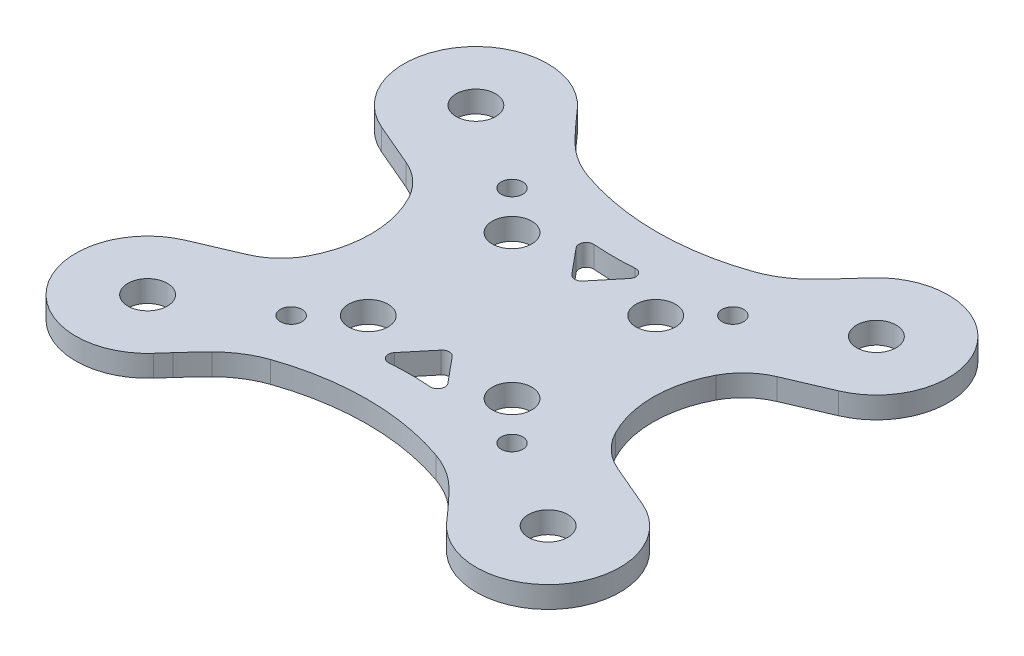
SolidWorks part; units mm, degrees
material "Thornel Mat VMA"
ref_plane "Front Plane" through (0, 0, 0) normal (0, 0, 1) x (1, 0, 0)
ref_plane "Top Plane" through (0, 0, 0) normal (0, 1, 0) x (1, 0, 0)
ref_plane "Right Plane" through (0, 0, 0) normal (1, 0, 0) x (0, 0, -1)
sketch "Sketch1" plane through (0, 0, 0) normal (0, 1, 0) x (1, 0, 0)
  line L0 (19.1123, 28.0515) -> (20.403, 29.4979)
  line L1 (31.7968, 13.6457) -> (25.7944, 11.0784)
  line L2 (25.7944, -11.0784) -> (31.7968, -13.6457)
  line L3 (20.403, -29.4979) -> (19.1123, -28.0515)
  line L4 (-19.1123, -28.0515) -> (-20.403, -29.4979)
  line L5 (-31.7968, -13.6457) -> (-25.7944, -11.0784)
  line L6 (-25.7944, 11.0784) -> (-31.7968, 13.6457)
  line L7 (-20.403, 29.4979) -> (-19.1123, 28.0515)
  line L8 (-0.7696, 9.0904) -> (-3.7105, 12.6352)
  line L9 (3.7105, 12.6352) -> (0.7696, 9.0904)
  line L10 (0.7696, -9.0904) -> (3.7105, -12.6352)
  line L11 (-3.7105, -12.6352) -> (-0.7696, -9.0904)
  circle A0 centre (27.8644, -22.84) radius 2.75
  circle A1 centre (-15.365, -15.365) radius 1.5
  circle A2 centre (15.365, 15.365) radius 1.5
  circle A3 centre (-15.365, 15.365) radius 1.5
  circle A4 centre (27.8644, 22.84) radius 2.75
  circle A5 centre (15.365, -15.365) radius 1.5
  circle A6 centre (10, 10) radius 2.75
  circle A7 centre (-10, 10) radius 2.75
  circle A8 centre (-10, -10) radius 2.75
  circle A9 centre (-27.8644, -22.84) radius 2.75
  circle A10 centre (-27.8644, 22.84) radius 2.75
  circle A11 centre (10, -10) radius 2.75
  arc A12 (16.4739, 25.2397) -> (19.1123, 28.0515) centre (-38.3402, 79.3175) ccw
  arc A13 (25.7944, 11.0784) -> (21.3765, 7.0088) centre (29.3336, 2.8035) ccw
  arc A14 (21.3765, 7.0088) -> (21.3765, -7.0088) centre (34.6384, 0) ccw
  arc A15 (21.3765, -7.0088) -> (25.7944, -11.0784) centre (29.3336, -2.8035) ccw
  arc A16 (20.403, -29.4979) -> (31.7968, -13.6457) centre (27.8644, -22.84) ccw
  arc A17 (19.1123, -28.0515) -> (16.4739, -25.2397) centre (-38.3402, -79.3175) ccw
  arc A18 (16.4739, -25.2397) -> (11.4857, -22.0897) centre (7.2196, -34.3697) ccw
  arc A19 (11.4857, -22.0897) -> (-11.4857, -22.0897) centre (0, -55.1514) ccw
  arc A20 (-11.4857, -22.0897) -> (-16.4739, -25.2397) centre (-7.2196, -34.3697) ccw
  arc A21 (-16.4739, -25.2397) -> (-19.1123, -28.0515) centre (38.3402, -79.3175) ccw
  arc A22 (-31.7968, -13.6457) -> (-20.403, -29.4979) centre (-27.8644, -22.84) ccw
  arc A23 (-25.7944, -11.0784) -> (-21.3765, -7.0088) centre (-29.3336, -2.8035) ccw
  arc A24 (-21.3765, -7.0088) -> (-21.3765, 7.0088) centre (-34.6384, 0) ccw
  arc A25 (-21.3765, 7.0088) -> (-25.7944, 11.0784) centre (-29.3336, 2.8035) ccw
  arc A26 (-20.403, 29.4979) -> (-31.7968, 13.6457) centre (-27.8644, 22.84) ccw
  arc A27 (-19.1123, 28.0515) -> (-16.4739, 25.2397) centre (38.3402, 79.3175) ccw
  arc A28 (-16.4739, 25.2397) -> (-11.4857, 22.0897) centre (-7.2196, 34.3697) ccw
  arc A29 (-11.4857, 22.0897) -> (11.4857, 22.0897) centre (0, 55.1514) ccw
  arc A30 (11.4857, 22.0897) -> (16.4739, 25.2397) centre (7.2196, 34.3697) ccw
  arc A31 (-0.7696, 9.0904) -> (0.7696, 9.0904) centre (0, 9.7289) ccw
  arc A32 (3.7105, 12.6352) -> (2.8655, 14.2709) centre (2.9409, 13.2737) ccw
  arc A33 (-2.8655, 14.2709) -> (2.8655, 14.2709) centre (0, 52.1627) ccw
  arc A34 (-2.8655, 14.2709) -> (-3.7105, 12.6352) centre (-2.9409, 13.2737) ccw
  arc A35 (2.8655, -14.2709) -> (3.7105, -12.6352) centre (2.9409, -13.2737) ccw
  arc A36 (0.7696, -9.0904) -> (-0.7696, -9.0904) centre (0, -9.7289) ccw
  arc A37 (-3.7105, -12.6352) -> (-2.8655, -14.2709) centre (-2.9409, -13.2737) ccw
  arc A38 (2.8655, -14.2709) -> (-2.8655, -14.2709) centre (0, -52.1627) ccw
  arc A39 (31.7968, 13.6457) -> (20.403, 29.4979) centre (27.8644, 22.84) ccw
sketch "Sketch2" plane through (0, 0, 0) normal (0, 1, 0) x (1, 0, 0)
  line L2 (3.7105, -12.6352) -> (0.7696, -9.0904)
  line L3 (-0.7696, -9.0904) -> (-3.7105, -12.6352)
  line L4 (3.7105, -12.6352) -> (0.7696, -9.0904)
  line L5 (-0.7696, -9.0904) -> (-3.7105, -12.6352)
  line L6 (-3.7105, 12.6352) -> (-0.7696, 9.0904)
  line L7 (0.7696, 9.0904) -> (3.7105, 12.6352)
  line L8 (-20.403, -29.4979) -> (-19.1123, -28.0515)
  line L9 (-25.7944, -11.0784) -> (-31.7968, -13.6457)
  line L10 (-31.7968, 13.6457) -> (-25.7944, 11.0784)
  line L11 (-19.1123, 28.0515) -> (-20.403, 29.4979)
  line L12 (20.403, 29.4979) -> (19.1123, 28.0515)
  line L13 (25.7944, 11.0784) -> (31.7968, 13.6457)
  line L14 (31.7968, -13.6457) -> (25.7944, -11.0784)
  line L15 (19.1123, -28.0515) -> (20.403, -29.4979)
  line L16 (-20.403, -29.4979) -> (-19.1123, -28.0515)
  line L17 (-25.7944, -11.0784) -> (-31.7968, -13.6457)
  line L18 (-31.7968, 13.6457) -> (-25.7944, 11.0784)
  line L19 (-19.1123, 28.0515) -> (-20.403, 29.4979)
  line L20 (20.403, 29.4979) -> (19.1123, 28.0515)
  line L21 (25.7944, 11.0784) -> (31.7968, 13.6457)
  line L22 (31.7968, -13.6457) -> (25.7944, -11.0784)
  line L23 (19.1123, -28.0515) -> (20.403, -29.4979)
  line L24 (-3.7105, 12.6352) -> (-0.7696, 9.0904)
  line L25 (0.7696, 9.0904) -> (3.7105, 12.6352)
  circle A1 centre (15.365, -15.365) radius 1.5
  circle A2 centre (15.365, -15.365) radius 1.5
  circle A3 centre (27.8644, 22.84) radius 2.75
  circle A4 centre (27.8644, 22.84) radius 2.75
  circle A5 centre (-15.365, 15.365) radius 1.5
  circle A6 centre (-15.365, 15.365) radius 1.5
  circle A7 centre (15.365, 15.365) radius 1.5
  circle A8 centre (15.365, 15.365) radius 1.5
  circle A9 centre (-15.365, -15.365) radius 1.5
  circle A10 centre (-15.365, -15.365) radius 1.5
  circle A11 centre (27.8644, -22.84) radius 2.75
  circle A12 centre (27.8644, -22.84) radius 2.75
  circle A13 centre (10, -10) radius 2.75
  circle A14 centre (10, -10) radius 2.75
  circle A15 centre (-27.8644, 22.84) radius 2.75
  circle A16 centre (-27.8644, 22.84) radius 2.75
  circle A17 centre (-27.8644, -22.84) radius 2.75
  circle A18 centre (-27.8644, -22.84) radius 2.75
  circle A19 centre (-10, -10) radius 2.75
  circle A20 centre (-10, -10) radius 2.75
  circle A21 centre (-10, 10) radius 2.75
  circle A22 centre (-10, 10) radius 2.75
  circle A23 centre (10, 10) radius 2.75
  circle A24 centre (10, 10) radius 2.75
  arc A28 (2.8655, -14.2709) -> (3.7105, -12.6352) centre (2.9409, -13.2737) ccw
  arc A29 (0.7696, -9.0904) -> (-0.7696, -9.0904) centre (0, -9.7289) ccw
  arc A30 (-3.7105, -12.6352) -> (-2.8655, -14.2709) centre (-2.9409, -13.2737) ccw
  arc A31 (2.8655, -14.2709) -> (-2.8655, -14.2709) centre (0, -52.1627) ccw
  arc A32 (2.8655, -14.2709) -> (3.7105, -12.6352) centre (2.9409, -13.2737) ccw
  arc A33 (0.7696, -9.0904) -> (-0.7696, -9.0904) centre (0, -9.7289) ccw
  arc A34 (-3.7105, -12.6352) -> (-2.8655, -14.2709) centre (-2.9409, -13.2737) ccw
  arc A35 (2.8655, -14.2709) -> (-2.8655, -14.2709) centre (0, -52.1627) ccw
  arc A36 (-2.8655, 14.2709) -> (2.8655, 14.2709) centre (0, 52.1627) ccw
  arc A37 (-2.8655, 14.2709) -> (-3.7105, 12.6352) centre (-2.9409, 13.2737) ccw
  arc A38 (-0.7696, 9.0904) -> (0.7696, 9.0904) centre (0, 9.7289) ccw
  arc A39 (3.7105, 12.6352) -> (2.8655, 14.2709) centre (2.9409, 13.2737) ccw
  arc A40 (-2.8655, 14.2709) -> (2.8655, 14.2709) centre (0, 52.1627) ccw
  arc A41 (-2.8655, 14.2709) -> (-3.7105, 12.6352) centre (-2.9409, 13.2737) ccw
  arc A42 (-0.7696, 9.0904) -> (0.7696, 9.0904) centre (0, 9.7289) ccw
  arc A43 (3.7105, 12.6352) -> (2.8655, 14.2709) centre (2.9409, 13.2737) ccw
  arc A44 (-16.4739, -25.2397) -> (-19.1123, -28.0515) centre (38.3402, -79.3175) ccw
  arc A45 (-31.7968, -13.6457) -> (-20.403, -29.4979) centre (-27.8644, -22.84) ccw
  arc A46 (-25.7944, -11.0784) -> (-21.3765, -7.0088) centre (-29.3336, -2.8035) ccw
  arc A47 (-21.3765, -7.0088) -> (-21.3765, 7.0088) centre (-34.6384, 0) ccw
  arc A48 (-21.3765, 7.0088) -> (-25.7944, 11.0784) centre (-29.3336, 2.8035) ccw
  arc A49 (-20.403, 29.4979) -> (-31.7968, 13.6457) centre (-27.8644, 22.84) ccw
  arc A50 (-19.1123, 28.0515) -> (-16.4739, 25.2397) centre (38.3402, 79.3175) ccw
  arc A51 (-16.4739, 25.2397) -> (-11.4857, 22.0897) centre (-7.2196, 34.3697) ccw
  arc A52 (-11.4857, 22.0897) -> (11.4857, 22.0897) centre (0, 55.1514) ccw
  arc A53 (11.4857, 22.0897) -> (16.4739, 25.2397) centre (7.2196, 34.3697) ccw
  arc A54 (16.4739, 25.2397) -> (19.1123, 28.0515) centre (-38.3402, 79.3175) ccw
  arc A55 (31.7968, 13.6457) -> (20.403, 29.4979) centre (27.8644, 22.84) ccw
  arc A56 (25.7944, 11.0784) -> (21.3765, 7.0088) centre (29.3336, 2.8035) ccw
  arc A57 (21.3765, 7.0088) -> (21.3765, -7.0088) centre (34.6384, 0) ccw
  arc A58 (21.3765, -7.0088) -> (25.7944, -11.0784) centre (29.3336, -2.8035) ccw
  arc A59 (20.403, -29.4979) -> (31.7968, -13.6457) centre (27.8644, -22.84) ccw
  arc A60 (19.1123, -28.0515) -> (16.4739, -25.2397) centre (-38.3402, -79.3175) ccw
  arc A61 (16.4739, -25.2397) -> (11.4857, -22.0897) centre (7.2196, -34.3697) ccw
  arc A62 (11.4857, -22.0897) -> (-11.4857, -22.0897) centre (0, -55.1514) ccw
  arc A63 (-11.4857, -22.0897) -> (-16.4739, -25.2397) centre (-7.2196, -34.3697) ccw
  arc A64 (-16.4739, -25.2397) -> (-19.1123, -28.0515) centre (38.3402, -79.3175) ccw
  arc A65 (-31.7968, -13.6457) -> (-20.403, -29.4979) centre (-27.8644, -22.84) ccw
  arc A66 (-25.7944, -11.0784) -> (-21.3765, -7.0088) centre (-29.3336, -2.8035) ccw
  arc A67 (-21.3765, -7.0088) -> (-21.3765, 7.0088) centre (-34.6384, 0) ccw
  arc A68 (-21.3765, 7.0088) -> (-25.7944, 11.0784) centre (-29.3336, 2.8035) ccw
  arc A69 (-20.403, 29.4979) -> (-31.7968, 13.6457) centre (-27.8644, 22.84) ccw
  arc A70 (-19.1123, 28.0515) -> (-16.4739, 25.2397) centre (38.3402, 79.3175) ccw
  arc A71 (-16.4739, 25.2397) -> (-11.4857, 22.0897) centre (-7.2196, 34.3697) ccw
  arc A72 (-11.4857, 22.0897) -> (11.4857, 22.0897) centre (0, 55.1514) ccw
  arc A73 (11.4857, 22.0897) -> (16.4739, 25.2397) centre (7.2196, 34.3697) ccw
  arc A74 (16.4739, 25.2397) -> (19.1123, 28.0515) centre (-38.3402, 79.3175) ccw
  arc A75 (31.7968, 13.6457) -> (20.403, 29.4979) centre (27.8644, 22.84) ccw
  arc A76 (25.7944, 11.0784) -> (21.3765, 7.0088) centre (29.3336, 2.8035) ccw
  arc A77 (21.3765, 7.0088) -> (21.3765, -7.0088) centre (34.6384, 0) ccw
  arc A78 (21.3765, -7.0088) -> (25.7944, -11.0784) centre (29.3336, -2.8035) ccw
  arc A79 (20.403, -29.4979) -> (31.7968, -13.6457) centre (27.8644, -22.84) ccw
  arc A80 (19.1123, -28.0515) -> (16.4739, -25.2397) centre (-38.3402, -79.3175) ccw
  arc A81 (16.4739, -25.2397) -> (11.4857, -22.0897) centre (7.2196, -34.3697) ccw
  arc A82 (11.4857, -22.0897) -> (-11.4857, -22.0897) centre (0, -55.1514) ccw
  arc A83 (-11.4857, -22.0897) -> (-16.4739, -25.2397) centre (-7.2196, -34.3697) ccw
  point P0 (0, 0)
  dimension "D1" = 0
  dimension "D2" = 0
  dimension "D3" = 0
  dimension "D4" = 0
  dimension "D5" = 0
  dimension "D6" = 0
  dimension "D7" = 0
  dimension "D8" = 0
  dimension "D9" = 0
  dimension "D10" = 0
  dimension "D11" = 0
  dimension "D12" = 0
  dimension "D13" = 0
  dimension "D14" = 0
  dimension "D15" = 0
extrude "Boss-Extrude1" add sketch "Sketch2" along normal blind 3
